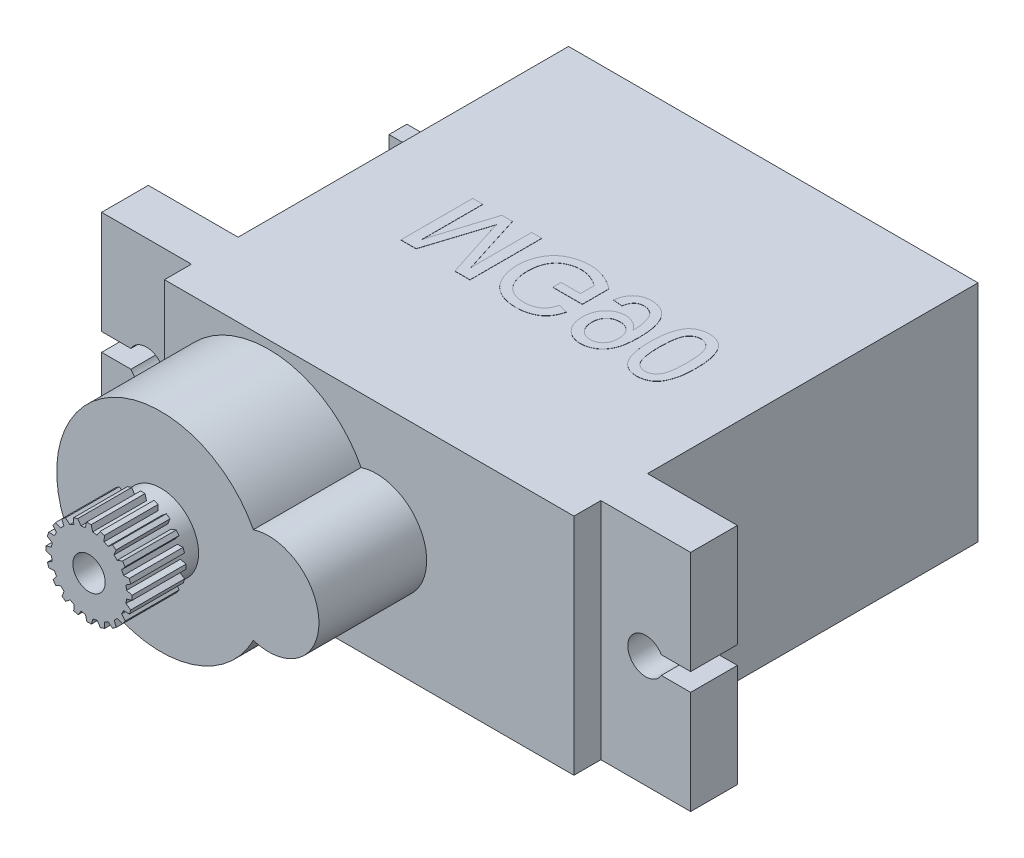
SolidWorks part; units mm, degrees
ref_plane "Спереди" through (0, 0, 0) normal (0, 0, 1) x (1, 0, 0)
ref_plane "Сверху" through (0, 0, 0) normal (0, 1, 0) x (1, 0, 0)
ref_plane "Справа" through (0, 0, 0) normal (1, 0, 0) x (0, 0, -1)
ref_axis "Ось1" through (0, 0, 50) along (0, 0, -1)
sketch "Эскиз1" plane through (0, 0, 0) normal (0, 0, 1) x (1, 0, 0)
  line L0 (-5.8, 0) -> (8.8, 0) construction
  arc A0 (5.15, 2.6679) -> (5.15, -2.6679) centre (0, 0) ccw
  arc A1 (5.15, -2.6679) -> (5.15, 2.6679) centre (6, 0) ccw
  dimension "D1" = 11.6
  dimension "D2" = 5.6
  dimension "D3" = 14.6
extrude "Бобышка-Вытянуть1" add sketch "Эскиз1" along normal blind 6
sketch "Эскиз2" plane through (0, 0, 6) normal (0, 0, 1) x (1, 0, 0)
  circle A0 centre (0, 0) radius 2.1
  circle A1 centre (0, 0) radius 0.9
  dimension "D1" = 4.2
  dimension "D2" = 1.8
extrude "Бобышка-Вытянуть2" add sketch "Эскиз2" along normal blind 4
sketch "Эскиз3" plane through (0, 0, 10) normal (0, 0, 1) x (1, 0, 0)
  line L1 (-0.2669, -1.8517) -> (0.2796, -1.8517)
  line L3 (0.1313, -2.3964) -> (0.2796, -1.8517)
  line L4 (-0.2669, -1.8517) -> (-0.1187, -2.3971)
  line L5 (-0.1187, -2.3971) -> (0.1313, -2.3964)
  circle A0 centre (0, 0) radius 2.4 construction
  point P5 (0.0063, -1.8517)
  point P7 (0.0063, -2.3967)
  dimension "D1" = 4.8
  dimension "D2" = 0.25
extrude "Бобышка-Вытянуть3" add sketch "Эскиз3" against normal blind 3
pattern_circular "Круговой массив1" count 20 over 360 about axis through (0, 0, 50) along (0, 0, -1) of "Бобышка-Вытянуть3"
sketch "Эскиз4" plane through (0, 0, 0) normal (0, 0, 1) x (1, 0, 0)
  line L1 (-5.8, 6.25) -> (17, 6.25)
  line L2 (-5.8, 6.25) -> (-5.8, -6.25)
  line L3 (-5.8, -6.25) -> (17, -6.25)
  line L4 (17, 6.25) -> (17, -6.25)
  arc A0 (5.15, 2.6679) -> (5.15, -2.6679) centre (0, 0) ccw construction
  point P4 (-5.8, 0)
  dimension "D1" = 22.8
  dimension "D2" = 12.5
extrude "Бобышка-Вытянуть4" add sketch "Эскиз4" against normal blind 22.5
sketch "Эскиз5" plane through (0, 0, 0) normal (0, 0, 1) x (1, 0, 0)
  line L0 (5.6, 6.25) -> (5.6, -6.25) construction
  line L1 (-5.8, 6.25) -> (-10.8, 6.25)
  line L2 (-5.8, 6.25) -> (-5.8, -6.25)
  line L3 (-5.8, -6.25) -> (-10.8, -6.25)
  line L4 (-10.8, 6.25) -> (-10.8, 0.5)
  line L5 (17, 6.25) -> (-5.8, 6.25) construction
  line L6 (-5.8, -6.25) -> (17, -6.25) construction
  line L7 (-9.166, 0.5) -> (-10.8, 0.5)
  line L9 (-10.8, -0.5) -> (-9.166, -0.5)
  line L11 (-10.8, -0.5) -> (-10.8, -6.25)
  line L12 (22, -0.5) -> (22, -6.25)
  line L13 (22, -0.5) -> (20.366, -0.5)
  line L14 (20.366, 0.5) -> (22, 0.5)
  line L15 (22, 6.25) -> (22, 0.5)
  line L16 (17, -6.25) -> (22, -6.25)
  line L17 (17, 6.25) -> (17, -6.25)
  line L18 (17, 6.25) -> (22, 6.25)
  arc A0 (-9.166, -0.5) -> (-9.166, 0.5) centre (-8.3, 0) ccw
  arc A1 (20.366, -0.5) -> (20.366, 0.5) centre (19.5, 0) cw
  point P9 (-8.3, 6.25)
  dimension "D3" = 1
  dimension "D1" = 5
  dimension "D2" = 1
extrude "Бобышка-Вытянуть5" add sketch "Эскиз5" against normal blind 2.6 from offset 1.5 offset against normal yes
sketch "Эскиз6" plane through (-5.8, 0, 0) normal (-1, 0, 0) x (0, 0, 1)
  line L1 (-18.5, 2) -> (-17.5, 2)
  line L2 (-18.5, 2) -> (-18.5, -2)
  line L3 (-18.5, -2) -> (-17.5, -2)
  line L4 (-17.5, 2) -> (-17.5, -2)
  point P4 (-17.5, 0)
  dimension "D1" = 1
  dimension "D2" = 4
  dimension "D3" = 4
extrude "Бобышка-Вытянуть6" add sketch "Эскиз6" along normal blind 5
sketch "Эскиз7" plane through (0, -6.25, 0) normal (0, -1, 0) x (1, 0, 0)
  text T0 "MG90"
extrude "Бобышка-Вытянуть7" add sketch "Эскиз7" along normal blind 0.01
mirror "Зеркальное отражение2" about plane through (0, 0, 0) normal (0, 1, 0) of "Бобышка-Вытянуть7"
